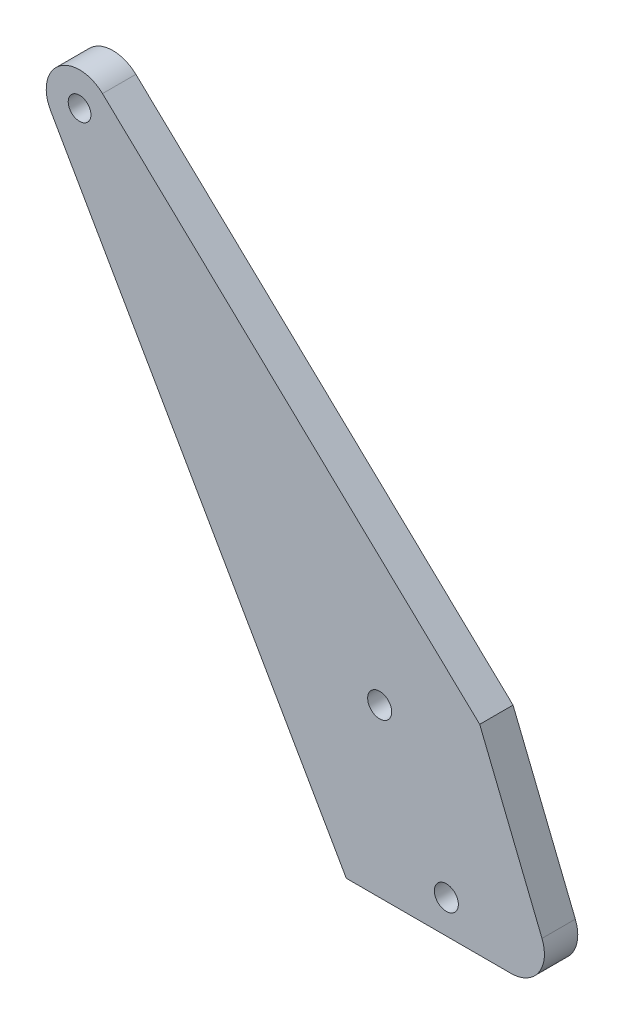
SolidWorks part; units mm, degrees
ref_plane "Front Plane" through (0, 0, 0) normal (0, 0, 1) x (1, 0, 0)
ref_plane "Top Plane" through (0, 0, 0) normal (0, 1, 0) x (1, 0, 0)
ref_plane "Right Plane" through (0, 0, 0) normal (1, 0, 0) x (0, 0, -1)
sketch "Sketch1" plane through (0, 0, 0) normal (0, 0, 1) x (1, 0, 0)
  line L1 (0, 0) -> (-25.4, 0)
  line L6 (-71.8309, 106.208) -> (0, 38.1)
  line L7 (-81.712, 98.4471) -> (-25.4, 0)
  line L8 (-323.85, -215.9) -> (44.45, -215.9) construction
  line L9 (0, 38.1) -> (15.3934, 0)
  line L10 (15.3934, 0) -> (0, 0)
  line L11 (0, 38.1) -> (0, 0) construction
  arc A1 (-71.8309, 106.208) -> (-81.712, 98.4471) centre (-76.2, 101.6) ccw
  circle A2 centre (-6.35, 6.35) radius 2.286
  circle A3 centre (-19.05, 31.75) radius 2.286
  circle A4 centre (-76.2, 101.6) radius 2.159
  dimension "D3" = 76.2
  dimension "D5" = 12.7
  dimension "D7" = 4.572
  dimension "D4" = 6.35
  dimension ".17" = 4.318
  dimension "D1" = 25.4
  dimension "D2" = 38.1
  dimension "D6" = 317.5
  dimension "D8" = 31.75
  dimension "D9" = 19.05
  dimension "D11" = 6.35
  dimension "D12" = 22
extrude "Boss-Extrude1" add sketch "Sketch1" against normal blind 6.35
fillet "Fillet1" radius 6.35 1 edges at (15.3934, 0, -3.175)
sketch "Sketch3" plane through (0, 0, 0) normal (0, 0, 1) x (1, 0, 0)
  line L0 (-76.2, 101.6) -> (-180.6644, -115.9152) construction
  line L1 (-13.2351, 71.3603) -> (-117.6994, -146.1549)
  line L2 (-139.1649, 131.8397) -> (-243.6293, -85.6756)
  line L3 (-76.2, 101.6) -> (-120.3423, 101.6) construction
  arc A0 (-13.2351, 71.3603) -> (-139.1649, 131.8397) centre (-76.2, 101.6) ccw
  arc A1 (-243.6293, -85.6756) -> (-117.6994, -146.1549) centre (-180.6644, -115.9152) ccw
  point P4 (-128.4322, -7.1576)
  dimension "D1" = 139.7
  dimension "D2" = 241.3
  dimension "D3" = 64.347
